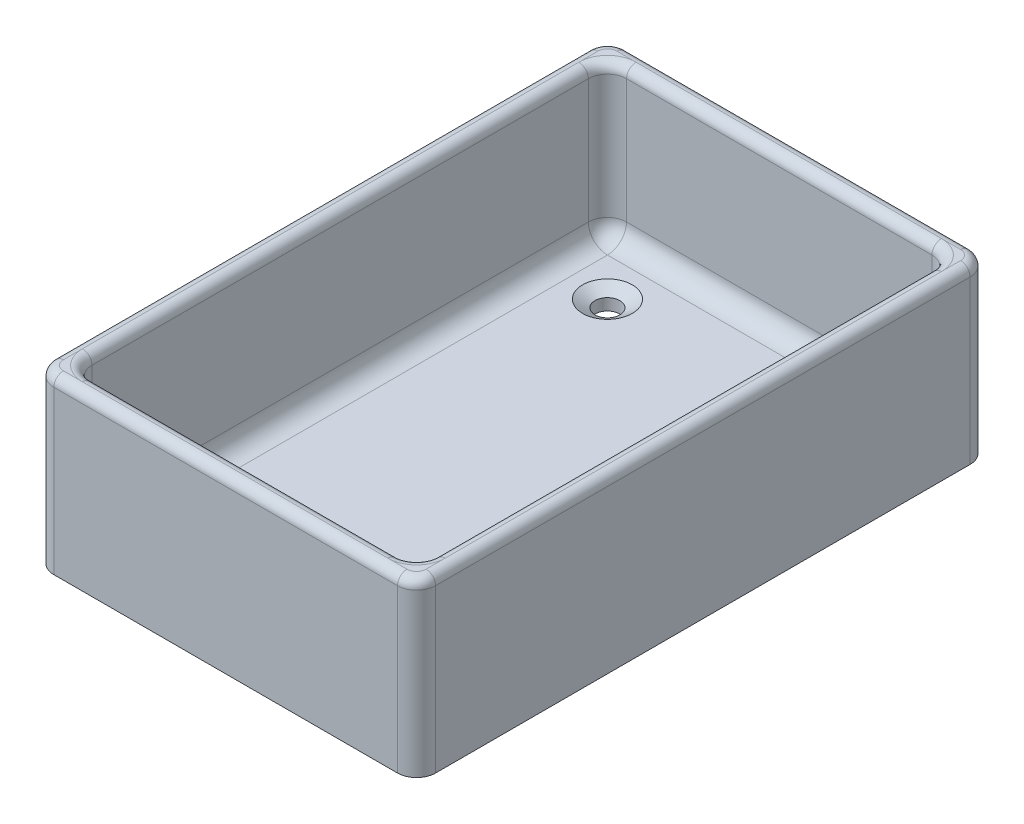
SolidWorks part; units mm, degrees
ref_plane "Front Plane" through (0, 0, 0) normal (0, 0, 1) x (1, 0, 0)
ref_plane "Top Plane" through (0, 0, 0) normal (0, 1, 0) x (1, 0, 0)
ref_plane "Right Plane" through (0, 0, 0) normal (1, 0, 0) x (0, 0, -1)
sketch "Sketch1" plane through (0, 0, 0) normal (0, 1, 0) x (1, 0, 0)
  line L1 (-28.575, -44.45) -> (28.575, -44.45)
  line L2 (-28.575, -44.45) -> (-28.575, 44.45)
  line L3 (-28.575, 44.45) -> (28.575, 44.45)
  line L4 (28.575, -44.45) -> (28.575, 44.45)
  line L5 (-28.575, -44.45) -> (28.575, 44.45) construction
  line L6 (-28.575, 44.45) -> (28.575, -44.45) construction
  point P0 (0, 0)
  dimension "D1" = 88.9
  dimension "D2" = 57.15
extrude "Extrude-Thin1" add sketch "Sketch1" along normal blind 25.4 thin thin type one direction wall 3.175
fillet "Fillet1" radius 3.175 8 edges at (-28.575, 12.7, 44.45) (28.575, 12.7, 44.45) (28.575, 12.7, -44.45) (-28.575, 12.7, -44.45) (31.75, 12.7, 47.625) (-31.75, 12.7, -47.625) (31.75, 12.7, -47.625) (-31.75, 12.7, 47.625)
sketch "Sketch2" plane through (0, 0, 0) normal (0, -1, 0) x (1, 0, 0)
  line L4 (31.75, -44.45) -> (31.75, 44.45)
  line L5 (28.575, 47.625) -> (-28.575, 47.625)
  line L6 (-31.75, 44.45) -> (-31.75, -44.45)
  line L7 (-28.575, -47.625) -> (28.575, -47.625)
  line L8 (31.75, -44.45) -> (31.75, 44.45)
  line L9 (28.575, 47.625) -> (-28.575, 47.625)
  line L10 (-31.75, 44.45) -> (-31.75, -44.45)
  line L11 (-28.575, -47.625) -> (28.575, -47.625)
  arc A4 (31.75, 44.45) -> (28.575, 47.625) centre (28.575, 44.45) ccw
  arc A5 (-28.575, 47.625) -> (-31.75, 44.45) centre (-28.575, 44.45) ccw
  arc A6 (-31.75, -44.45) -> (-28.575, -47.625) centre (-28.575, -44.45) ccw
  arc A7 (28.575, -47.625) -> (31.75, -44.45) centre (28.575, -44.45) ccw
  arc A8 (31.75, 44.45) -> (28.575, 47.625) centre (28.575, 44.45) ccw
  arc A9 (-28.575, 47.625) -> (-31.75, 44.45) centre (-28.575, 44.45) ccw
  arc A10 (-31.75, -44.45) -> (-28.575, -47.625) centre (-28.575, -44.45) ccw
  arc A11 (28.575, -47.625) -> (31.75, -44.45) centre (28.575, -44.45) ccw
  dimension "D1" = 0
extrude "Boss-Extrude1" add sketch "Sketch2" along normal blind 3.175
fillet "Fillet2" radius 3.175 8 edges at (0, 0, -44.45) (27.6451, 0, -43.5201) (28.575, 0, 0) (27.6451, 0, 43.5201) (0, 0, 44.45) (-27.6451, 0, 43.5201) (-28.575, 0, 0) (-27.6451, 0, -43.5201)
sketch "Sketch3" plane through (0, 0, 0) normal (0, 1, 0) x (1, 0, 0)
  line L0 (-25.4, 41.275) -> (-19.05, 34.925) construction
  line L1 (0, 0) -> (-19.05, 0) construction
  line L2 (0, 0) -> (0, 34.925) construction
  line L3 (0, 34.925) -> (-19.05, 34.925) construction
  line L4 (-19.05, 0) -> (-19.05, 34.925) construction
  circle A0 centre (-19.05, 34.925) radius 2.0637
  dimension "D3" = 4.1275
  dimension "D1" = 135
  dimension "D2" = 6.35
extrude "Cut-Extrude1" cut sketch "Sketch3" against normal blind 3.175
ref_axis "Axis1" through (-19.05, -3.175, -34.925) along (0, 1, 0)
ref_plane "Plane1" through (0, 0, -34.925) normal (0, 0, -1) x (0, 1, 0)
sketch "Sketch4" plane through (0, 0, -34.925) normal (0, 0, -1) x (0, 1, 0)
  line L0 (-2.4801, -19.05) -> (0, -14.9225)
  line L1 (-3.175, -19.05) -> (0, -19.05) construction
  line L2 (0, 25.4) -> (0, -25.4) construction
  line L3 (0, -14.9225) -> (0, -19.05)
  line L4 (0, -19.05) -> (-2.4801, -19.05) construction
  line L5 (-2.4801, -19.05) -> (0, -19.05)
  dimension "D1" = 59
  dimension "D2" = 4.1275
revolve "Cut-Revolve1" cut sketch "Sketch4" angle 360 about L4
ref_axis "Axis2" through (0, 26.8287, 0) along (0, -1, 0)
pattern_circular "CirPattern1" count 2 over 360 about axis through (0, 26.8287, 0) along (0, -1, 0) of "Cut-Extrude1", "Cut-Revolve1"
fillet "Fillet3" radius 1.5875 16 edges at (30.8201, 25.4, -46.6951) (31.75, 25.4, 0) (30.8201, 25.4, 46.6951) (0, 25.4, 47.625) (-30.8201, 25.4, 46.6951) (-31.75, 25.4, 0) (-30.8201, 25.4, -46.6951) (27.6451, 25.4, 43.5201) (0, 25.4, 44.45) (-27.6451, 25.4, 43.5201) (-28.575, 25.4, 0) (-27.6451, 25.4, -43.5201) (0, 25.4, -44.45) (27.6451, 25.4, -43.5201) (0, 25.4, -47.625) (28.575, 25.4, 0)
